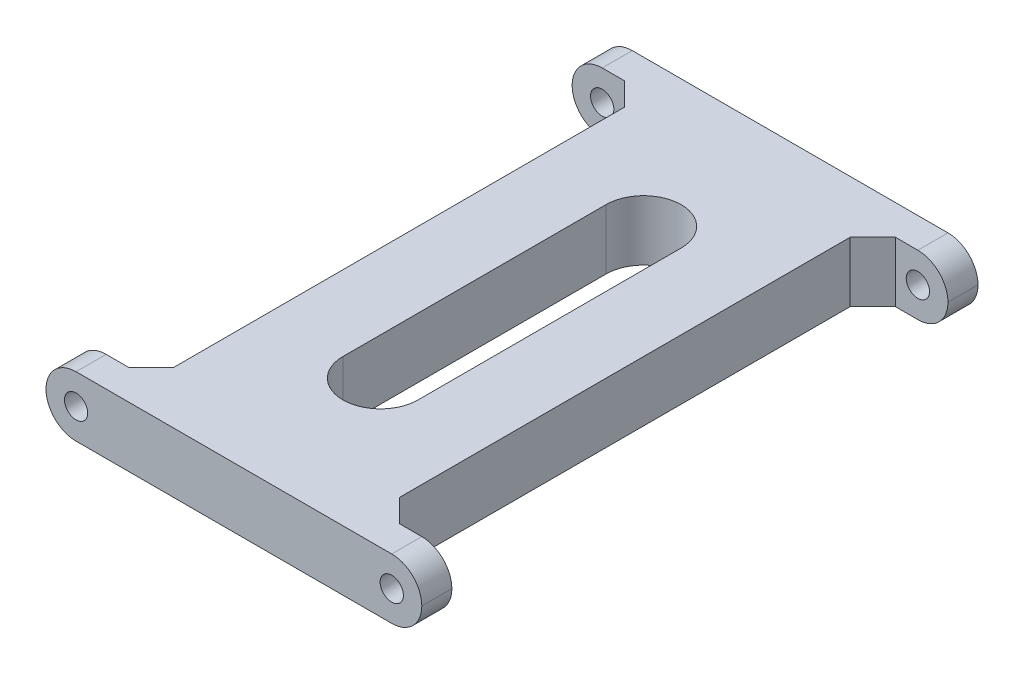
SolidWorks part; units mm, degrees
material "6061 Alloy"
ref_plane "前视基准面" through (0, 0, 0) normal (0, 0, 1) x (1, 0, 0)
ref_plane "上视基准面" through (0, 0, 0) normal (0, 1, 0) x (1, 0, 0)
ref_plane "右视基准面" through (0, 0, 0) normal (1, 0, 0) x (0, 0, -1)
sketch "Sketch1" plane through (0, 0, 0) normal (0, 1, 0) x (1, 0, 0)
  line L0 (0, 0) -> (0, 26.9649) construction
  line L1 (0, 0) -> (41.2475, 0) construction
  line L2 (-25, 37) -> (25, 37)
  line L3 (25, 37) -> (25, 33)
  line L4 (25, 33) -> (15, 33)
  line L5 (15, 33) -> (15, -33)
  line L6 (-15, 33) -> (-15, -33)
  line L7 (-25, 33) -> (-15, 33)
  line L8 (-25, 37) -> (-25, 33)
  line L9 (-25, -37) -> (-25, -33)
  line L10 (-25, -33) -> (-15, -33)
  line L11 (25, -33) -> (15, -33)
  line L12 (25, -37) -> (25, -33)
  line L13 (-25, -37) -> (25, -37)
  line L14 (0, -17.5) -> (0, 17.5) construction
  line L15 (-5, -17.5) -> (-5, 17.5)
  line L16 (5, -17.5) -> (5, 17.5)
  arc A0 (-5, -17.5) -> (5, -17.5) centre (0, -17.5) ccw
  arc A1 (5, 17.5) -> (-5, 17.5) centre (0, 17.5) ccw
  point P13 (0, 37)
  point P16 (-15, 0)
  point P17 (15, 0)
  point P21 (0, 0)
  dimension "D6" = 5
  dimension "D1" = 25
  dimension "D2" = 4
  dimension "D3" = 10
  dimension "D4" = 74
  dimension "D5" = 35
extrude "Boss-Extrude1" add sketch "Sketch1" along normal mid plane 8
chamfer "Chamfer1" distance 3 angle 45 4 edges at (15, 0, 33) (-15, 0, 33) (-15, 0, -33) (15, 0, -33)
sketch "Sketch3" plane through (0, 0, 0) normal (0, 0, 1) x (1, 0, 0)
  line L0 (0, 0) -> (-42.1534, 0) construction
  line L1 (-25, 4) -> (-25, -4) construction
  line L2 (0, 0) -> (0, -12.8718) construction
  circle A0 centre (-21, 0) radius 1.55
  circle A1 centre (21, 0) radius 1.55
  dimension "D1" = 4
  dimension "D2" = 3.1
extrude "Cut-Extrude1" cut sketch "Sketch3" against normal through all both and the other way through all
fillet "Fillet1" radius 4 8 edges at (25, -4, 35) (-25, -4, 35) (-25, 4, 35) (25, 4, 35) (25, -4, -35) (25, 4, -35) (-25, -4, -35) (-25, 4, -35)
